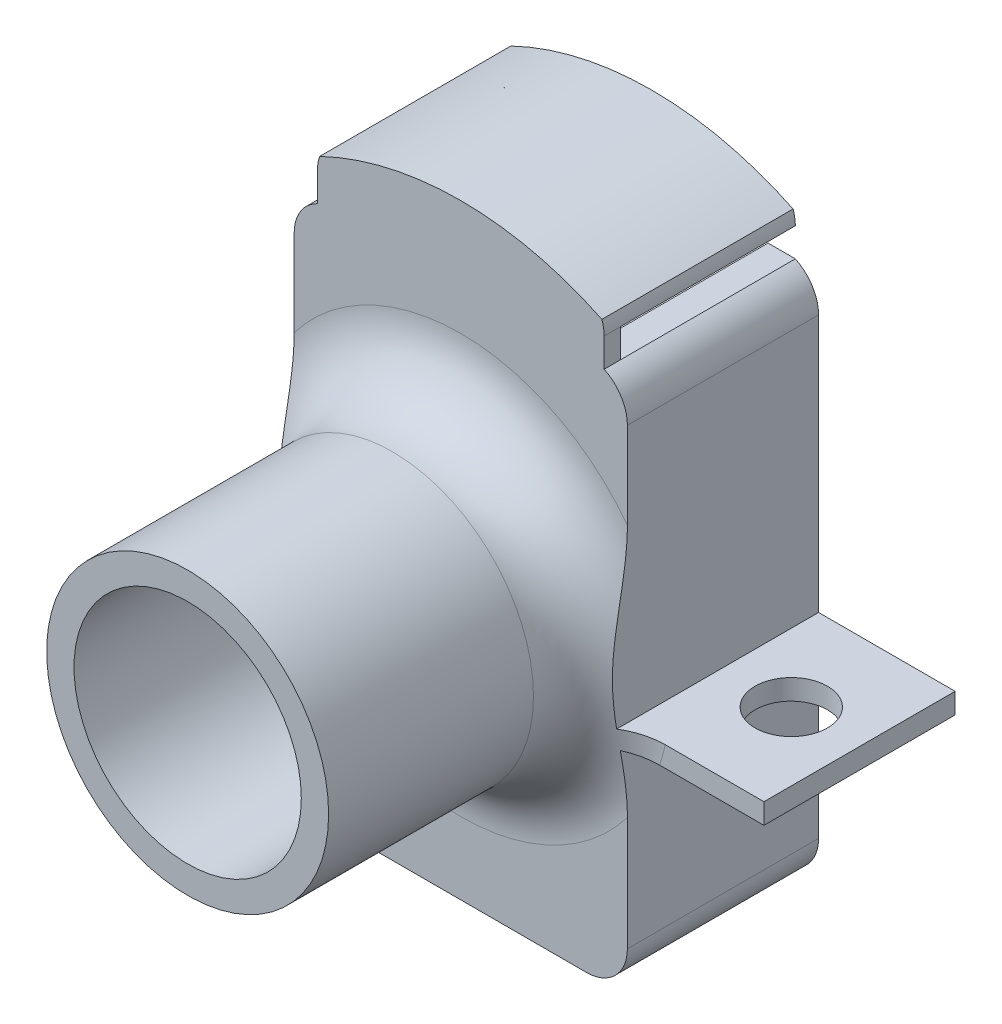
SolidWorks part; units mm, degrees
ref_plane "Front Plane" through (0, 0, 0) normal (0, 0, 1) x (1, 0, 0)
ref_plane "Top Plane" through (0, 0, 0) normal (0, 1, 0) x (1, 0, 0)
ref_plane "Right Plane" through (0, 0, 0) normal (1, 0, 0) x (0, 0, -1)
sketch "Sketch1" plane through (0, 0, 0) normal (1, 0, 0) x (0, 0, -1)
  line L0 (0, 0) -> (59.0662, 0) construction
  line L1 (0, 10.5705) -> (25.4, 10.5705)
  line L2 (25.4, 10.5705) -> (25.4, 7.9375)
  line L3 (25.4, 7.9375) -> (43.18, 7.9375)
  line L4 (43.18, 7.9375) -> (43.18, 30.1625)
  line L5 (43.18, 30.1625) -> (25.4, 30.1625)
  line L6 (25.4, 30.1625) -> (25.4, 19.4605)
  line L7 (19.05, 13.1105) -> (0, 13.1105)
  line L8 (0, 13.1105) -> (0, 10.5705)
  line L10 (43.18, 0) -> (26.924, 0) construction
  line L11 (43.18, 0) -> (43.18, 26.0812) construction
  line L12 (43.18, 26.0812) -> (26.924, 26.0812) construction
  line L13 (26.924, 0) -> (26.924, 26.0812) construction
  arc A0 (25.4, 19.4605) -> (19.05, 13.1105) centre (19.05, 19.4605) cw
  dimension "D4" = 6.35
  dimension "D1" = 21.1409
  dimension "D2" = 2.54
  dimension "D3" = 25.4
  dimension "D5" = 43.18
  dimension "D6" = 60.325
  dimension "D7" = 16.256
  dimension "D8" = 15.875
revolve "Body" add sketch "Sketch1" angle 360 about L0
sketch "Sketch2" plane through (0, 0, -43.18) normal (0, 0, -1) x (-1, 0, 0)
  line L0 (0, -1.27) -> (0, 27.178) construction
  line L1 (-11.684, -23.622) -> (11.684, -23.622)
  line L2 (-12.954, -22.352) -> (-12.954, 19.812)
  line L3 (-11.684, 21.082) -> (-10.795, 21.082)
  line L4 (12.954, -22.352) -> (12.954, 19.812)
  line L5 (-12.954, -23.622) -> (12.954, 21.082) construction
  line L6 (-12.954, 21.082) -> (12.954, -23.622) construction
  line L7 (-15.494, -22.352) -> (-15.494, -6.0601)
  line L8 (-13.335, 23.2457) -> (-13.335, 23.2457)
  line L9 (-9.525, 27.178) -> (9.525, 27.178)
  line L10 (-13.335, 23.2457) -> (-13.335, 25.908)
  line L11 (-10.795, 21.082) -> (-10.795, 25.908)
  line L12 (10.795, 21.082) -> (11.684, 21.082)
  line L13 (10.795, 21.082) -> (10.795, 25.908)
  line L14 (-9.525, 29.718) -> (9.525, 29.718)
  line L15 (13.335, 23.2457) -> (13.335, 25.908)
  line L16 (13.335, 23.2457) -> (13.335, 23.2457)
  line L17 (15.494, -22.352) -> (15.494, 19.812)
  line L18 (-11.684, -26.162) -> (11.684, -26.162)
  line L19 (-15.494, -4.1551) -> (-15.494, 19.812)
  line L20 (-28.194, -4.1551) -> (-15.494, -4.1551)
  line L21 (-28.194, -4.1551) -> (-28.194, -6.0601)
  line L22 (-28.194, -6.0601) -> (-15.494, -6.0601)
  line L23 (-13.335, 25.908) -> (-10.795, 25.908)
  line L24 (-15.494, -22.352) -> (-15.494, 19.812) construction
  line L25 (-13.335, 23.2457) -> (-10.795, 23.2457)
  circle A0 centre (0, 0) radius 28.8925 construction
  circle A1 centre (0, 0) radius 30.1625 construction
  arc A2 (-11.684, 21.082) -> (-12.954, 19.812) centre (-11.684, 19.812) ccw
  arc A3 (-9.525, 27.178) -> (-10.795, 25.908) centre (-9.525, 25.908) ccw
  arc A4 (9.525, 27.178) -> (10.795, 25.908) centre (9.525, 25.908) cw
  arc A5 (11.684, 21.082) -> (12.954, 19.812) centre (11.684, 19.812) cw
  arc A6 (12.954, -22.352) -> (11.684, -23.622) centre (11.684, -22.352) cw
  arc A7 (-11.684, -23.622) -> (-12.954, -22.352) centre (-11.684, -22.352) cw
  arc A8 (-13.335, 23.2457) -> (-15.494, 19.812) centre (-11.684, 19.812) ccw
  arc A9 (-9.525, 29.718) -> (-13.335, 25.908) centre (-9.525, 25.908) ccw
  arc A10 (9.525, 29.718) -> (13.335, 25.908) centre (9.525, 25.908) cw
  arc A11 (13.335, 23.2457) -> (15.494, 19.812) centre (11.684, 19.812) cw
  arc A12 (15.494, -22.352) -> (11.684, -26.162) centre (11.684, -22.352) cw
  arc A13 (-11.684, -26.162) -> (-15.494, -22.352) centre (-11.684, -22.352) cw
  point P0 (0, -1.27)
  point P21 (-10.795, 27.178)
  point P24 (10.795, 27.178)
  circle M7 centre (0, 0) radius 30.1625
  circle M8 centre (0, 0) radius 7.9375
  dimension "D5" = 1.27
  dimension "D8" = 1.27
  dimension "D1" = 44.704
  dimension "D2" = 25.908
  dimension "D3" = 50.8
  dimension "D4" = 21.59
  dimension "D6" = 1.27
  dimension "D7" = 6.096
  dimension "D10" = 12.7
  dimension "D11" = 1.905
  dimension "D9" = 2.54
extrude "Battery holder" cut sketch "Sketch2" against normal blind 16.256 contours A7 L1 A6 L4 A5 L12 L13 A4 L9 A3 L11 L3 A2 L2 M8 | L10 L25 L11 L23 region at (12.1788, -22.8468, -43.18) region at (12.065, 24.5769, -43.18)
extrude "Cut-Extrude3" cut sketch "Sketch2<3>" against normal blind 26.416 contours L18 A13 L7 L22 L21 L20 L19 A8 L10 A9 A10 L15 A11 L17 A12 M7 region at (15.6139, 22.283, -43.18)
sketch "Sketch2<3>" plane through (0, 0, -43.18) normal (0, 0, -1) x (-1, 0, 0) same geometry as "Sketch2"
sketch "Sketch3" plane through (0, -6.0601, 0) normal (0, -1, 0) x (1, 0, 0)
  line L0 (28.194, -43.18) -> (15.494, -25.4) construction
  line L3 (15.494, -24.7377) -> (15.494, -43.18) construction
  line L4 (28.194, -25.4) -> (18.4928, -25.4) construction
  circle A0 centre (21.844, -34.29) radius 3.368
  dimension "D1" = 6.7361
extrude "Panel Mount" cut sketch "Sketch3" against normal blind 16.256
sketch "Sketch4" plane through (0, 0, -25.4) normal (0, 0, 1) x (1, 0, 0)
  line L0 (0, 11.8405) -> (0, 9.3005) construction
  line L1 (1.2319, 11.8405) -> (1.2319, 9.3005)
  line L2 (-1.2319, 11.8405) -> (-1.2319, 9.3005)
  line L3 (0, -11.8405) -> (0, -9.3005) construction
  line L4 (-1.2319, -11.8405) -> (-1.2319, -9.3005)
  line L5 (1.2319, -11.8405) -> (1.2319, -9.3005)
  circle A0 centre (0, 0) radius 3.175
  circle A1 centre (8.763, 0) radius 1.9431
  circle A2 centre (-8.763, 0) radius 1.9431
  circle A3 centre (0, 5.16) radius 1.1011
  circle A4 centre (0, -5.16) radius 1.1011
  circle A5 centre (0, 0) radius 10.5705 construction
  circle A6 centre (0, 0) radius 6.2611 construction
  circle A7 centre (0, 0) radius 8.763 construction
  arc A8 (1.2319, 11.8405) -> (-1.2319, 11.8405) centre (0, 11.8405) ccw
  arc A9 (-1.2319, 9.3005) -> (1.2319, 9.3005) centre (0, 9.3005) ccw
  arc A10 (-1.2319, -11.8405) -> (1.2319, -11.8405) centre (0, -11.8405) ccw
  arc A11 (1.2319, -9.3005) -> (-1.2319, -9.3005) centre (0, -9.3005) ccw
  circle A12 centre (0, 0) radius 10.5705 construction
  point P15 (0, 10.5705)
  point P22 (0, -10.5705)
  circle M1 centre (0, 0) radius 7.9375
  circle M2 centre (0, 0) radius 10.5705
  dimension "D1" = 6.35
  dimension "D2" = 2.2022
  dimension "D3" = 12.5222
  dimension "D4" = 17.526
  dimension "D5" = 3.8862
  dimension "D6" = 2.4638
  dimension "D7" = 1.27
extrude "Wings" add sketch "Sketch4" along normal blind 1.27 contours L2 L1 M2 M1 | L2 A9 L1 M1 | L5 A11 L4 M1 | L5 L4 M2 M1 region at (0, 9.4227, -25.4) region at (0, -9.4227, -25.4)
extrude "Electronic Axis" cut sketch "Sketch4<3>" against normal blind 6.35 contours A2 M1 M2 | A1 M2 M1 region at (9.1117, 0, -25.4) region at (-9.1117, 0, -25.4)
sketch "Sketch4<3>" plane through (0, 0, -25.4) normal (0, 0, 1) x (1, 0, 0) same geometry as "Sketch4"
